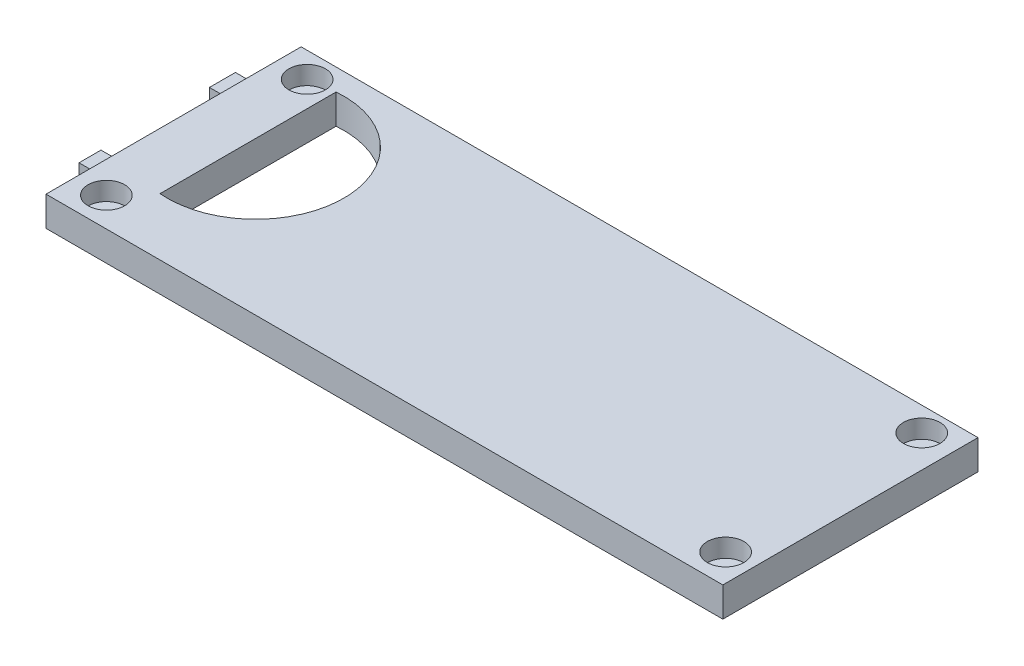
SolidWorks part; units mm, degrees
ref_plane "Front Plane" through (0, 0, 0) normal (0, 0, 1) x (1, 0, 0)
ref_plane "Top Plane" through (0, 0, 0) normal (0, 1, 0) x (1, 0, 0)
ref_plane "Right Plane" through (0, 0, 0) normal (1, 0, 0) x (0, 0, -1)
sketch "Sketch1" plane through (0, 0, 0) normal (0, 1, 0) x (1, 0, 0)
  line L1 (57, -21.4874) -> (-57, -21.4874)
  line L2 (57, -21.4874) -> (57, 21.4874)
  line L3 (57, 21.4874) -> (-57, 21.4874)
  line L4 (-57, -21.4874) -> (-57, 21.4874)
  line L5 (57, -21.4874) -> (-57, 21.4874) construction
  line L6 (57, 21.4874) -> (-57, -21.4874) construction
  point P0 (0, 0)
extrude "Boss-Extrude1" add sketch "Sketch1" along normal blind 5
sketch "Sketch2" plane through (0, 5, 0) normal (0, 1, 0) x (1, 0, 0)
  line L0 (-57, 21.4874) -> (-53.5, 21.4874) construction
  line L1 (57, 21.4874) -> (-57, 21.4874) construction
sketch "Sketch3" plane through (0, 5, 0) normal (0, 1, 0) x (1, 0, 0)
  line L0 (-51.7531, 23.5004) -> (-51.7531, -21.2397) construction
  line L1 (57.5677, 22.3499) -> (57.5677, -22.3902) construction
  line L2 (-55.25, 21.4874) -> (-55.25, -21.4874) construction
  line L3 (-57, 21.4874) -> (-53.5, 21.4874) construction
  line L4 (-57, -21.4874) -> (57, -21.4874) construction
  line L9 (-57, 0) -> (57, 0) construction
  line L10 (-57, 21.4874) -> (-57, -21.4874) construction
  line L11 (57, -21.4874) -> (57, 21.4874) construction
  line L12 (-51.7531, 17.2469) -> (51.585, 17.4252) construction
  line L13 (-0.0841, 17.3361) -> (-0.0841, -21.4874) construction
  line L14 (0, 0) -> (0, -21.4874) construction
  line L15 (-51.7531, -16.5649) -> (55.5178, -16.4581) construction
  line L16 (51.585, 17.4252) -> (52.4378, -16.4581) construction
  circle A0 centre (-51.7531, 17.2469) radius 3.08
  circle A1 centre (-51.7531, -16.5649) radius 3.08
  circle A2 centre (51.585, 17.4252) radius 3.08
  circle A3 centre (52.4378, -16.4581) radius 3.08
extrude "Cut-Extrude1" cut sketch "Sketch3" against normal blind 3.1
sketch "Sketch5" plane through (-57, 0, 0) normal (-1, 0, 0) x (0, 0, 1)
  line L0 (-22.3979, 2.4922) -> (22.3422, 2.4922) construction
  line L1 (-13.513, 1.7003) -> (-13.513, 3.7003)
  line L2 (-13.513, 1.7003) -> (-9.1383, 1.7003)
  line L3 (-9.1383, 1.7003) -> (-9.1383, 3.7003)
  line L4 (-13.513, 3.7003) -> (-9.1383, 3.7003)
  line L5 (-9.1383, 1.7003) -> (9.1276, 1.7003) construction
  line L9 (12.8259, 3.6937) -> (9.1276, 3.6937)
  line L10 (9.1276, 1.6901) -> (9.1276, 3.6937)
  line L11 (12.8259, 1.6901) -> (9.1276, 1.6901)
  line L12 (12.8259, 1.6901) -> (12.8259, 3.6937)
  line L13 (-21.4874, 2.5) -> (21.4874, 2.5) construction
  line L14 (-21.4874, 5) -> (-21.4874, 0) construction
  line L15 (21.4874, 5) -> (21.4874, 0) construction
  point P2 (-11.2129, 2.4922)
  point P11 (11.1572, 2.4922)
  dimension "D1" = 2
extrude "Boss-Extrude2" add sketch "Sketch5" along normal blind 3.1
sketch "Sketch6" plane through (0, 5, 0) normal (0, 1, 0) x (1, 0, 0)
  circle A0 centre (0, 0) radius 15
extrude "Boss-Extrude3" [suppressed] add sketch "Sketch6" along normal blind 8
sketch "Sketch8" [suppressed] plane through (0, 13, 0) normal (0, 1, 0) x (1, 0, 0)
  circle A0 centre (0, 0) radius 14.5
extrude "Cut-Extrude2" [suppressed] cut sketch "Sketch8" against normal blind 4.6
sketch "Sketch9" [suppressed] plane through (0, 8.4, 0) normal (0, 1, 0) x (1, 0, 0)
  line L0 (-18.3405, -5.4356) -> (20.9474, -5.4356)
  line L1 (20.9474, -5.4356) -> (20.9474, 6.4298)
  line L2 (20.9474, 6.4298) -> (-18.3405, 6.4298)
  line L3 (-18.3405, 6.4298) -> (-18.3405, -5.4356)
extrude "Cut-Extrude5" [suppressed] cut sketch "Sketch9" along normal blind 9.6
ref_plane "Plane1" [suppressed] through (13.9805, 13, 5.4356) normal (0.3624, 0, -0.932) x (-0.932, 0, -0.3624)
sketch "Sketch11" [suppressed] plane through (0, 13, 0) normal (0, 1, 0) x (1, 0, 0)
  line L0 (-2.0086, -12.4834) -> (-2.0086, -14.8138)
  line L1 (0, -12.4834) -> (-2.0086, -12.4834)
  line L3 (-2.0086, -12.4834) -> (3.0728, -12.4834)
  line L5 (3.0728, -12.4834) -> (3.0728, -14.6075)
  arc A3 (-2.0086, -14.8138) -> (3.0728, -14.6075) centre (-0.1027, 0.9217) ccw
extrude "Boss-Extrude5" [suppressed] add sketch "Sketch11" along normal blind 1 contours L3 L5 A3 L0
sketch "Sketch12" plane through (0, 0, 0) normal (0, -1, 0) x (1, 0, 0)
  line L0 (0, 14.5) -> (0, -14.5) construction
  line L1 (-15, 0) -> (15, 0) construction
  line L17 (-1.3814, -4.9711) -> (-0.1328, -4.2503)
  line L36 (-0.1328, -4.2503) -> (-0.1328, -2.8085)
  line L37 (-0.1328, -2.8085) -> (-1.3814, -2.0876)
  line L38 (-1.3814, -2.0876) -> (-2.63, -2.8085)
  line L39 (-2.63, -2.8085) -> (-2.63, -4.2503)
  line L40 (-2.63, -4.2503) -> (-1.3814, -4.9711)
  line L46 (-4.2896, -4.9711) -> (-3.041, -4.2503)
  line L47 (-3.041, -4.2503) -> (-3.041, -2.8085)
  line L48 (-3.041, -2.8085) -> (-4.2896, -2.0876)
  line L49 (-4.2896, -2.0876) -> (-5.5382, -2.8085)
  line L50 (-5.5382, -2.8085) -> (-5.5382, -4.2503)
  line L51 (-5.5382, -4.2503) -> (-4.2896, -4.9711)
  line L52 (4.5464, -5.001) -> (5.795, -4.2801)
  line L53 (5.795, -4.2801) -> (5.795, -2.8384)
  line L54 (5.795, -2.8384) -> (4.5464, -2.1175)
  line L55 (4.5464, -2.1175) -> (3.2978, -2.8384)
  line L56 (3.2978, -2.8384) -> (3.2978, -4.2801)
  line L57 (3.2978, -4.2801) -> (4.5464, -5.001)
  line L58 (1.6382, -5.001) -> (2.8868, -4.2801)
  line L59 (2.8868, -4.2801) -> (2.8868, -2.8384)
  line L60 (2.8868, -2.8384) -> (1.6382, -2.1175)
  line L61 (1.6382, -2.1175) -> (0.3896, -2.8384)
  line L62 (0.3896, -2.8384) -> (0.3896, -4.2801)
  line L63 (0.3896, -4.2801) -> (1.6382, -5.001)
  line L64 (-1.4428, -1.2342) -> (-0.1942, -0.5133)
  line L65 (-0.1942, -0.5133) -> (-0.1942, 0.9284)
  line L66 (-0.1942, 0.9284) -> (-1.4428, 1.6493)
  line L67 (-1.4428, 1.6493) -> (-2.6914, 0.9284)
  line L68 (-2.6914, 0.9284) -> (-2.6914, -0.5133)
  line L69 (-2.6914, -0.5133) -> (-1.4428, -1.2342)
  line L70 (-4.351, -1.2342) -> (-3.1025, -0.5133)
  line L71 (-3.1025, -0.5133) -> (-3.1025, 0.9284)
  line L72 (-3.1025, 0.9284) -> (-4.351, 1.6493)
  line L73 (-4.351, 1.6493) -> (-5.5996, 0.9284)
  line L74 (-5.5996, 0.9284) -> (-5.5996, -0.5133)
  line L75 (-5.5996, -0.5133) -> (-4.351, -1.2342)
  line L76 (4.4849, -1.2641) -> (5.7335, -0.5432)
  line L77 (5.7335, -0.5432) -> (5.7335, 0.8985)
  line L78 (5.7335, 0.8985) -> (4.4849, 1.6194)
  line L79 (4.4849, 1.6194) -> (3.2363, 0.8985)
  line L80 (3.2363, 0.8985) -> (3.2363, -0.5432)
  line L81 (3.2363, -0.5432) -> (4.4849, -1.2641)
  line L82 (1.5767, -1.2641) -> (2.8253, -0.5432)
  line L83 (2.8253, -0.5432) -> (2.8253, 0.8985)
  line L84 (2.8253, 0.8985) -> (1.5767, 1.6194)
  line L85 (1.5767, 1.6194) -> (0.3281, 0.8985)
  line L86 (0.3281, 0.8985) -> (0.3281, -0.5432)
  line L87 (0.3281, -0.5432) -> (1.5767, -1.2641)
  line L88 (-1.4428, 2.3085) -> (-0.1942, 3.0293)
  line L89 (-0.1942, 3.0293) -> (-0.1942, 4.4711)
  line L90 (-0.1942, 4.4711) -> (-1.4428, 5.192)
  line L91 (-1.4428, 5.192) -> (-2.6914, 4.4711)
  line L92 (-2.6914, 4.4711) -> (-2.6914, 3.0293)
  line L93 (-2.6914, 3.0293) -> (-1.4428, 2.3085)
  line L94 (-4.351, 2.3085) -> (-3.1025, 3.0293)
  line L95 (-3.1025, 3.0293) -> (-3.1025, 4.4711)
  line L96 (-3.1025, 4.4711) -> (-4.351, 5.192)
  line L97 (-4.351, 5.192) -> (-5.5996, 4.4711)
  line L98 (-5.5996, 4.4711) -> (-5.5996, 3.0293)
  line L99 (-5.5996, 3.0293) -> (-4.351, 2.3085)
  line L100 (4.4849, 2.2786) -> (5.7335, 2.9995)
  line L101 (5.7335, 2.9995) -> (5.7335, 4.4412)
  line L102 (5.7335, 4.4412) -> (4.4849, 5.1621)
  line L103 (4.4849, 5.1621) -> (3.2363, 4.4412)
  line L104 (3.2363, 4.4412) -> (3.2363, 2.9995)
  line L105 (3.2363, 2.9995) -> (4.4849, 2.2786)
  line L106 (1.5767, 2.2786) -> (2.8253, 2.9995)
  line L107 (2.8253, 2.9995) -> (2.8253, 4.4412)
  line L108 (2.8253, 4.4412) -> (1.5767, 5.1621)
  line L109 (1.5767, 5.1621) -> (0.3281, 4.4412)
  line L110 (0.3281, 4.4412) -> (0.3281, 2.9995)
  line L111 (0.3281, 2.9995) -> (1.5767, 2.2786)
  line L112 (-1.4248, 5.5165) -> (-0.1763, 6.2374)
  line L113 (-0.1763, 6.2374) -> (-0.1763, 7.6792)
  line L114 (-0.1763, 7.6792) -> (-1.4248, 8.4)
  line L115 (-1.4248, 8.4) -> (-2.6734, 7.6792)
  line L116 (-2.6734, 7.6792) -> (-2.6734, 6.2374)
  line L117 (-2.6734, 6.2374) -> (-1.4248, 5.5165)
  line L118 (-4.3331, 5.5165) -> (-3.0845, 6.2374)
  line L119 (-3.0845, 6.2374) -> (-3.0845, 7.6792)
  line L120 (-3.0845, 7.6792) -> (-4.3331, 8.4)
  line L121 (-4.3331, 8.4) -> (-5.5816, 7.6792)
  line L122 (-5.5816, 7.6792) -> (-5.5816, 6.2374)
  line L123 (-5.5816, 6.2374) -> (-4.3331, 5.5165)
  line L124 (4.5029, 5.4867) -> (5.7515, 6.2075)
  line L125 (5.7515, 6.2075) -> (5.7515, 7.6493)
  line L126 (5.7515, 7.6493) -> (4.5029, 8.3702)
  line L127 (4.5029, 8.3702) -> (3.2543, 7.6493)
  line L128 (3.2543, 7.6493) -> (3.2543, 6.2075)
  line L129 (3.2543, 6.2075) -> (4.5029, 5.4867)
  line L130 (1.5947, 5.4867) -> (2.8433, 6.2075)
  line L131 (2.8433, 6.2075) -> (2.8433, 7.6493)
  line L132 (2.8433, 7.6493) -> (1.5947, 8.3702)
  line L133 (1.5947, 8.3702) -> (0.3461, 7.6493)
  line L134 (0.3461, 7.6493) -> (0.3461, 6.2075)
  line L135 (0.3461, 6.2075) -> (1.5947, 5.4867)
  line L136 (-1.4064, 8.9229) -> (-0.1579, 9.6438)
  line L137 (-0.1579, 9.6438) -> (-0.1579, 11.0856)
  line L138 (-0.1579, 11.0856) -> (-1.4064, 11.8064)
  line L139 (-1.4064, 11.8064) -> (-2.655, 11.0856)
  line L140 (-2.655, 11.0856) -> (-2.655, 9.6438)
  line L141 (-2.655, 9.6438) -> (-1.4064, 8.9229)
  line L142 (-4.3147, 8.9229) -> (-3.0661, 9.6438)
  line L143 (-3.0661, 9.6438) -> (-3.0661, 11.0856)
  line L144 (-3.0661, 11.0856) -> (-4.3147, 11.8064)
  line L145 (-4.3147, 11.8064) -> (-5.5633, 11.0856)
  line L146 (-5.5633, 11.0856) -> (-5.5633, 9.6438)
  line L147 (-5.5633, 9.6438) -> (-4.3147, 8.9229)
  line L148 (4.5213, 8.8931) -> (5.7699, 9.6139)
  line L149 (5.7699, 9.6139) -> (5.7699, 11.0557)
  line L150 (5.7699, 11.0557) -> (4.5213, 11.7766)
  line L151 (4.5213, 11.7766) -> (3.2727, 11.0557)
  line L152 (3.2727, 11.0557) -> (3.2727, 9.6139)
  line L153 (3.2727, 9.6139) -> (4.5213, 8.8931)
  line L154 (1.6131, 8.8931) -> (2.8617, 9.6139)
  line L155 (2.8617, 9.6139) -> (2.8617, 11.0557)
  line L156 (2.8617, 11.0557) -> (1.6131, 11.7766)
  line L157 (1.6131, 11.7766) -> (0.3645, 11.0557)
  line L158 (0.3645, 11.0557) -> (0.3645, 9.6139)
  line L159 (0.3645, 9.6139) -> (1.6131, 8.8931)
  line L160 (-1.4667, -8.5789) -> (-0.2181, -7.858)
  line L161 (-0.2181, -7.858) -> (-0.2181, -6.4163)
  line L162 (-0.2181, -6.4163) -> (-1.4667, -5.6954)
  line L163 (-1.4667, -5.6954) -> (-2.7153, -6.4163)
  line L164 (-2.7153, -6.4163) -> (-2.7153, -7.858)
  line L165 (-2.7153, -7.858) -> (-1.4667, -8.5789)
  line L166 (-4.3749, -8.5789) -> (-3.1263, -7.858)
  line L167 (-3.1263, -7.858) -> (-3.1263, -6.4163)
  line L168 (-3.1263, -6.4163) -> (-4.3749, -5.6954)
  line L169 (-4.3749, -5.6954) -> (-5.6235, -6.4163)
  line L170 (-5.6235, -6.4163) -> (-5.6235, -7.858)
  line L171 (-5.6235, -7.858) -> (-4.3749, -8.5789)
  line L172 (4.461, -8.6088) -> (5.7096, -7.8879)
  line L173 (5.7096, -7.8879) -> (5.7096, -6.4461)
  line L174 (5.7096, -6.4461) -> (4.461, -5.7253)
  line L175 (4.461, -5.7253) -> (3.2124, -6.4461)
  line L176 (3.2124, -6.4461) -> (3.2124, -7.8879)
  line L177 (3.2124, -7.8879) -> (4.461, -8.6088)
  line L178 (1.5528, -8.6088) -> (2.8014, -7.8879)
  line L179 (2.8014, -7.8879) -> (2.8014, -6.4461)
  line L180 (2.8014, -6.4461) -> (1.5528, -5.7253)
  line L181 (1.5528, -5.7253) -> (0.3042, -6.4461)
  line L182 (0.3042, -6.4461) -> (0.3042, -7.8879)
  line L183 (0.3042, -7.8879) -> (1.5528, -8.6088)
  line L184 (-1.5025, -12.1629) -> (-0.2539, -11.442)
  line L185 (-0.2539, -11.442) -> (-0.2539, -10.0003)
  line L186 (-0.2539, -10.0003) -> (-1.5025, -9.2794)
  line L187 (-1.5025, -9.2794) -> (-2.7511, -10.0003)
  line L188 (-2.7511, -10.0003) -> (-2.7511, -11.442)
  line L189 (-2.7511, -11.442) -> (-1.5025, -12.1629)
  line L190 (-4.4107, -12.1629) -> (-3.1621, -11.442)
  line L191 (-3.1621, -11.442) -> (-3.1621, -10.0003)
  line L192 (-3.1621, -10.0003) -> (-4.4107, -9.2794)
  line L193 (-4.4107, -9.2794) -> (-5.6593, -10.0003)
  line L194 (-5.6593, -10.0003) -> (-5.6593, -11.442)
  line L195 (-5.6593, -11.442) -> (-4.4107, -12.1629)
  line L196 (4.4253, -12.1928) -> (5.6739, -11.4719)
  line L197 (5.6739, -11.4719) -> (5.6739, -10.0301)
  line L198 (5.6739, -10.0301) -> (4.4253, -9.3093)
  line L199 (4.4253, -9.3093) -> (3.1767, -10.0301)
  line L200 (3.1767, -10.0301) -> (3.1767, -11.4719)
  line L201 (3.1767, -11.4719) -> (4.4253, -12.1928)
  line L202 (1.5171, -12.1928) -> (2.7657, -11.4719)
  line L203 (2.7657, -11.4719) -> (2.7657, -10.0301)
  line L204 (2.7657, -10.0301) -> (1.5171, -9.3093)
  line L205 (1.5171, -9.3093) -> (0.2685, -10.0301)
  line L206 (0.2685, -10.0301) -> (0.2685, -11.4719)
  line L207 (0.2685, -11.4719) -> (1.5171, -12.1928)
  line L208 (-6.2102, -1.2905) -> (-6.9311, -0.0419)
  line L209 (-6.9311, -0.0419) -> (-8.3728, -0.0419)
  line L210 (-8.3728, -0.0419) -> (-9.0937, -1.2905)
  line L211 (-9.0937, -1.2905) -> (-8.3728, -2.539)
  line L212 (-8.3728, -2.539) -> (-6.9311, -2.539)
  line L213 (-6.9311, -2.539) -> (-6.2102, -1.2905)
  line L214 (-6.2102, -4.1987) -> (-6.9311, -2.9501)
  line L215 (-6.9311, -2.9501) -> (-8.3728, -2.9501)
  line L216 (-8.3728, -2.9501) -> (-9.0937, -4.1987)
  line L217 (-9.0937, -4.1987) -> (-8.3728, -5.4473)
  line L218 (-8.3728, -5.4473) -> (-6.9311, -5.4473)
  line L219 (-6.9311, -5.4473) -> (-6.2102, -4.1987)
  line L220 (-6.1803, 4.6373) -> (-6.9012, 5.8859)
  line L221 (-6.9012, 5.8859) -> (-8.3429, 5.8859)
  line L222 (-8.3429, 5.8859) -> (-9.0638, 4.6373)
  line L223 (-9.0638, 4.6373) -> (-8.3429, 3.3887)
  line L224 (-8.3429, 3.3887) -> (-6.9012, 3.3887)
  line L225 (-6.9012, 3.3887) -> (-6.1803, 4.6373)
  line L226 (-6.1803, 1.7291) -> (-6.9012, 2.9777)
  line L227 (-6.9012, 2.9777) -> (-8.3429, 2.9777)
  line L228 (-8.3429, 2.9777) -> (-9.0638, 1.7291)
  line L229 (-9.0638, 1.7291) -> (-8.3429, 0.4805)
  line L230 (-8.3429, 0.4805) -> (-6.9012, 0.4805)
  line L231 (-6.9012, 0.4805) -> (-6.1803, 1.7291)
  line L232 (9.3641, -1.6319) -> (8.6432, -0.3833)
  line L233 (8.6432, -0.3833) -> (7.2014, -0.3833)
  line L234 (7.2014, -0.3833) -> (6.4806, -1.6319)
  line L235 (6.4806, -1.6319) -> (7.2014, -2.8804)
  line L236 (7.2014, -2.8804) -> (8.6432, -2.8804)
  line L237 (8.6432, -2.8804) -> (9.3641, -1.6319)
  line L238 (9.3641, -4.5401) -> (8.6432, -3.2915)
  line L239 (8.6432, -3.2915) -> (7.2014, -3.2915)
  line L240 (7.2014, -3.2915) -> (6.4806, -4.5401)
  line L241 (6.4806, -4.5401) -> (7.2014, -5.7887)
  line L242 (7.2014, -5.7887) -> (8.6432, -5.7887)
  line L243 (8.6432, -5.7887) -> (9.3641, -4.5401)
  line L244 (9.3939, 4.2959) -> (8.6731, 5.5445)
  line L245 (8.6731, 5.5445) -> (7.2313, 5.5445)
  line L246 (7.2313, 5.5445) -> (6.5104, 4.2959)
  line L247 (6.5104, 4.2959) -> (7.2313, 3.0473)
  line L248 (7.2313, 3.0473) -> (8.6731, 3.0473)
  line L249 (8.6731, 3.0473) -> (9.3939, 4.2959)
  line L250 (9.3939, 1.3877) -> (8.6731, 2.6363)
  line L251 (8.6731, 2.6363) -> (7.2313, 2.6363)
  line L252 (7.2313, 2.6363) -> (6.5104, 1.3877)
  line L253 (6.5104, 1.3877) -> (7.2313, 0.1391)
  line L254 (7.2313, 0.1391) -> (8.6731, 0.1391)
  line L255 (8.6731, 0.1391) -> (9.3939, 1.3877)
  circle A0 centre (-1.4248, 6.9583) radius 1.2486 construction
  circle A12 centre (-1.3814, -3.5294) radius 1.2486 construction
  circle A14 centre (-4.2896, -3.5294) radius 1.2486 construction
  circle A15 centre (4.5464, -3.5593) radius 1.2486 construction
  circle A16 centre (1.6382, -3.5593) radius 1.2486 construction
  circle A17 centre (-1.4428, 0.2075) radius 1.2486 construction
  circle A18 centre (-4.351, 0.2075) radius 1.2486 construction
  circle A19 centre (4.4849, 0.1777) radius 1.2486 construction
  circle A20 centre (1.5767, 0.1777) radius 1.2486 construction
  circle A21 centre (-1.4428, 3.7502) radius 1.2486 construction
  circle A22 centre (-4.351, 3.7502) radius 1.2486 construction
  circle A23 centre (4.4849, 3.7203) radius 1.2486 construction
  circle A24 centre (1.5767, 3.7203) radius 1.2486 construction
  circle A25 centre (-4.3331, 6.9583) radius 1.2486 construction
  circle A26 centre (4.5029, 6.9284) radius 1.2486 construction
  circle A27 centre (1.5947, 6.9284) radius 1.2486 construction
  circle A28 centre (-1.4064, 10.3647) radius 1.2486 construction
  circle A29 centre (-4.3147, 10.3647) radius 1.2486 construction
  circle A30 centre (4.5213, 10.3348) radius 1.2486 construction
  circle A31 centre (1.6131, 10.3348) radius 1.2486 construction
  circle A32 centre (-1.4667, -7.1372) radius 1.2486 construction
  circle A33 centre (-4.3749, -7.1372) radius 1.2486 construction
  circle A34 centre (4.461, -7.167) radius 1.2486 construction
  circle A35 centre (1.5528, -7.167) radius 1.2486 construction
  circle A36 centre (-1.5025, -10.7211) radius 1.2486 construction
  circle A37 centre (-4.4107, -10.7211) radius 1.2486 construction
  circle A38 centre (4.4253, -10.751) radius 1.2486 construction
  circle A39 centre (1.5171, -10.751) radius 1.2486 construction
  circle A40 centre (-7.6519, -1.2905) radius 1.2486 construction
  circle A41 centre (-7.6519, -4.1987) radius 1.2486 construction
  circle A42 centre (-7.6221, 4.6373) radius 1.2486 construction
  circle A43 centre (-7.6221, 1.7291) radius 1.2486 construction
  circle A44 centre (7.9223, -1.6319) radius 1.2486 construction
  circle A45 centre (7.9223, -4.5401) radius 1.2486 construction
  circle A46 centre (7.9522, 4.2959) radius 1.2486 construction
  circle A47 centre (7.9522, 1.3877) radius 1.2486 construction
extrude "Cut-Extrude6" [suppressed] cut sketch "Sketch12" against normal blind 10
sketch "Sketch13" plane through (0, 0, 0) normal (0, -1, 0) x (1, 0, 0)
  line L0 (-57, 21.4874) -> (-47.4692, 21.4874)
  line L1 (-57, 21.4874) -> (57, 21.4874) construction
  line L2 (-47.4692, 21.4874) -> (-47.4692, -21.4874) construction
  line L3 (57, -21.4874) -> (-57, -21.4874) construction
  line L4 (-47.4692, 11.8194) -> (-47.4692, -17.8397)
  arc A0 (-47.4692, 11.8194) -> (-47.4692, -17.8397) centre (-46.2068, -3.0101) cw
extrude "Cut-Extrude7" cut sketch "Sketch13" against normal blind 10 contours A0 L4 region at (-40.5666, 0, -3.0101)
